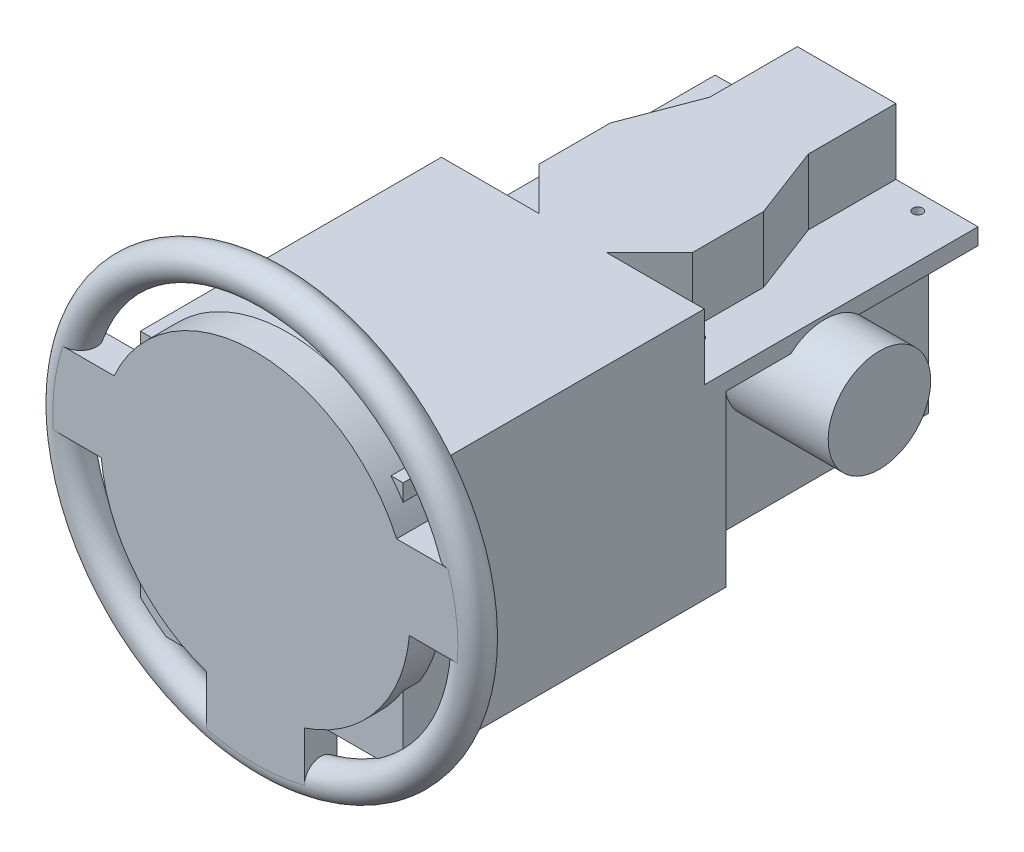
SolidWorks part; units mm, degrees
ref_plane "Płaszczyzna przednia" through (0, 0, 0) normal (0, 0, 1) x (1, 0, 0)
ref_plane "Płaszczyzna górna" through (0, 0, 0) normal (0, 1, 0) x (1, 0, 0)
ref_plane "Płaszczyzna prawa" through (0, 0, 0) normal (1, 0, 0) x (0, 0, -1)
sketch "Szkic4" plane through (0, 0, 0) normal (0, 1, 0) x (1, 0, 0)
  line L0 (0, 0) -> (0, -14.1713) construction
  line L1 (0, 0) -> (-185, 0) construction
  circle A0 centre (-185, 0) radius 15
  dimension "D1" = 30
  dimension "D2" = 185
revolve "Obrót2" add sketch "Szkic4" angle 360 about L0
sketch "Szkic5" plane through (0, 0, 0) normal (0, 0, 1) x (1, 0, 0)
  line L0 (0, 141.2771) -> (0, -223.1934) construction
  line L1 (-175.7848, 57.6603) -> (-128.9748, 57.6603)
  line L2 (-184.5472, -12.936) -> (-140.6836, -12.936)
  line L3 (-44.7738, -133.9945) -> (-44.7738, -179.5002)
  line L4 (44.7738, -133.9945) -> (44.7738, -179.5002)
  line L5 (128.9748, 57.6603) -> (175.7848, 57.6603)
  line L6 (140.6836, -12.936) -> (184.5472, -12.936)
  line L7 (-170, 0) -> (-200, 0) construction
  arc A0 (-140.6836, -12.936) -> (-44.7738, -133.9945) centre (0, 0) ccw
  arc A1 (-175.7848, 57.6603) -> (-184.5472, -12.936) centre (0, 0) ccw
  arc A2 (44.7738, -133.9945) -> (140.6836, -12.936) centre (0, 0) ccw
  arc A3 (128.9748, 57.6603) -> (-128.9748, 57.6603) centre (0, 0) ccw
  arc A4 (-44.7738, -179.5002) -> (44.7738, -179.5002) centre (0, 0) ccw
  arc A5 (184.5472, -12.936) -> (175.7848, 57.6603) centre (0, 0) ccw
  circle A6 centre (0, 0) radius 170 construction
  circle A7 centre (0, 0) radius 200 construction
  circle A8 centre (0, 0) radius 185 construction
  point P23 (-185, 0)
extrude "Dodanie-wyciągnięcie1" add sketch "Szkic5" against normal blind 15 and the other way blind 15 separate body contours L3 A4 L4 A2 L6 A5 L5 A3 L1 A1 L2 A0
sketch "Szkic6" plane through (0, 0, 0) normal (0, 1, 0) x (1, 0, 0)
  line L0 (0, -15) -> (0, 525) construction
  line L3 (-185, -15) -> (185, -15) construction
  dimension "D1" = 540
sketch "Szkic7" plane through (0, 0, 0) normal (0, 0, 1) x (1, 0, 0)
  line L0 (120, 90) -> (-120, -140) construction
  line L1 (120, 90) -> (-120, 90)
  line L2 (120, 90) -> (120, -140)
  line L3 (120, -140) -> (-120, -140)
  line L4 (-120, 90) -> (-120, -140)
  line L5 (-120, 90) -> (120, -140) construction
  line L6 (0, -140) -> (0, 0) construction
  dimension "D1" = 240
  dimension "D2" = 230
  dimension "D3" = 140
extrude "Dodanie-wyciągnięcie2" add sketch "Szkic7" against normal up to vertex (525 mm away) up to point (0, 0, -525)
sketch "Szkic8" plane through (0, 0, 0) normal (0, 1, 0) x (1, 0, 0)
  line L0 (0, -15) -> (0, 485)
  line L1 (0, -15) -> (0, 525) construction
  point P5 (0, 0)
  dimension "D1" = 500
sketch "Szkic9" plane through (0, 0, -525) normal (0, 0, -1) x (-1, 0, 0)
  line L0 (120, -74.5601) -> (120, 74.5601) construction
  line L1 (-120, 90) -> (120, 90)
  line L2 (-120, 90) -> (-120, 30)
  line L3 (-120, 30) -> (120, 30)
  line L4 (120, 90) -> (120, 30)
  line L6 (-70, 30) -> (70, 30)
  line L7 (-70, 30) -> (-70, 90)
  line L8 (-70, 90) -> (70, 90)
  line L9 (70, 30) -> (70, 90)
  point P11 (0, 90)
  point P12 (0, 90)
  line M5 (-120, 90) -> (-120, -140)
  line M7 (120, -140) -> (120, 90)
  line M8 (120, 90) -> (-120, 90)
  dimension "D1" = 60
  dimension "D2" = 140
extrude "Wytnij-wyciągnięcie1" cut sketch "Szkic9" against normal blind 250 contours L3 L7 L1 M5 | L9 L3 M7 M8 region at (95, 60, -525) region at (-95, 60, -525)
sketch "Szkic10" plane through (0, 0, -525) normal (0, 0, -1) x (-1, 0, 0)
  line L0 (120, -140) -> (-120, -140) construction
  line L1 (-75, -140) -> (75, -140)
  line L2 (-75, -140) -> (-75, 15)
  line L3 (-75, 15) -> (75, 15)
  line L4 (75, -140) -> (75, 15)
  line L5 (120, 30) -> (120, -140) construction
  line L6 (-120, -140) -> (120, -140)
  line L7 (-120, -140) -> (-120, 15)
  line L8 (-120, 15) -> (120, 15)
  line L9 (120, -140) -> (120, 15)
  line L10 (-120, 30) -> (-70, 30) construction
  point P13 (0, 15)
  point P14 (0, 15)
  line M10 (-120, 30) -> (-120, -140)
  line M11 (-120, -140) -> (120, -140)
  line M12 (120, -140) -> (120, 30)
  dimension "D1" = 150
  dimension "D2" = 15
extrude "Wytnij-wyciągnięcie2" cut sketch "Szkic10" against normal blind 230 contours L8 L4 M11 M12 | L8 L2 M10 M11 region at (97.5, -62.5, -525) region at (-97.5, -62.5, -525)
sketch "Szkic11" plane through (0, 30, 0) normal (0, 1, 0) x (1, 0, 0)
  line L0 (120, 525) -> (70, 525) construction
  line L1 (0, -15) -> (0, 525) construction
  circle A0 centre (80, 510) radius 4.5
  circle A1 centre (80, 310) radius 4.5
  circle A2 centre (-80, 310) radius 4.5
  circle A3 centre (-80, 510) radius 4.5
  dimension "D1" = 9
  dimension "D2" = 160
  dimension "D3" = 160
  dimension "D4" = 200
  dimension "D5" = 15
  dimension "D6" = 80
extrude "Wytnij-wyciągnięcie3" cut sketch "Szkic11" against normal blind 230
sketch "Szkic12" plane through (0, 0, -525) normal (0, 0, -1) x (-1, 0, 0)
  line L0 (75, -140) -> (75, 15) construction
  line L1 (-75, 15) -> (75, 15)
  line L2 (-75, 15) -> (-75, -25)
  line L3 (-75, -25) -> (75, -25)
  line L4 (75, 15) -> (75, -25)
  line L6 (-45, 15) -> (45, 15)
  line L7 (-45, 15) -> (-45, -25)
  line L8 (-45, -25) -> (45, -25)
  line L9 (45, 15) -> (45, -25)
  point P11 (0, -25)
  point P12 (0, -25)
  line M9 (75, -140) -> (75, 15)
  line M15 (-75, 15) -> (-75, -140)
  dimension "D1" = 90
  dimension "D2" = 40
extrude "Wytnij-wyciągnięcie4" cut sketch "Szkic12" against normal up to surface (230 mm away) contours L7 L1 L3 M15 | L1 L9 L3 M9 region at (60, -5, -525) region at (-60, -5, -525) up to face at (97.5, -62.5, -295)
sketch "Szkic13" plane through (120, 0, 0) normal (1, 0, 0) x (0, 0, -1)
  line L0 (525, -140) -> (525, -25) construction
  line L1 (275, 90) -> (0, 90) construction
  circle A0 centre (385, -20) radius 46.8123
  dimension "D1" = 140
  dimension "D2" = 110
extrude "Dodanie-wyciągnięcie3" add sketch "Szkic13" against normal up to surface (75 mm away) and the other way blind 50 up to face at (45, -5, -410)
sketch "Szkic14" plane through (0, 90, 0) normal (0, 1, 0) x (1, 0, 0)
  line L0 (70, 314.1421) -> (30.8579, 275)
  line L1 (70, 275) -> (70, 525) construction
  line L2 (30.8579, 275) -> (-30.8579, 275)
  line L3 (120, 275) -> (70, 275) construction
  line L4 (0, -15) -> (0, 525) construction
  line L5 (70, 379.1421) -> (45, 445)
  line L6 (70, 275) -> (70, 525) construction
  line L8 (70, 314.1421) -> (70, 379.1421)
  line L9 (45, 445) -> (45, 525)
  line L10 (70, 525) -> (-70, 525) construction
  line L11 (45, 525) -> (-45, 525)
  line L12 (0, -220) -> (0, 220) construction
  line L13 (-45, 445) -> (-45, 525)
  line L14 (-70, 379.1421) -> (-45, 445)
  line L15 (-70, 314.1421) -> (-70, 379.1421)
  line L16 (-70, 314.1421) -> (-30.8579, 275)
  line L18 (70, 275) -> (-70, 275)
  line L19 (70, 275) -> (70, 525)
  line L20 (70, 525) -> (-70, 525)
  line L21 (-70, 275) -> (-70, 525)
  circle A1 centre (80, 310) radius 4.5 construction
  point P23 (0, 525)
  point P27 (0, 275)
  line M11 (70, 275) -> (70, 525)
  line M12 (70, 525) -> (-70, 525)
  line M13 (-70, 525) -> (-70, 275)
  dimension "D1" = 10
  dimension "D2" = 45
  dimension "D3" = 80
  dimension "D4" = 45
  dimension "D5" = 65
extrude "Wytnij-wyciągnięcie5" cut sketch "Szkic14" against normal up to surface (60 mm away) contours L18 L0 M11 | L18 L16 M13 | L14 L13 M13 M12 | L9 L5 M11 M12 region at (56.9526, 90, -288.0474) region at (58.715, 90, -466.9352) region at (-56.9526, 90, -288.0474) region at (-58.715, 90, -466.9352) up to face at (80, 30, -305.5)
